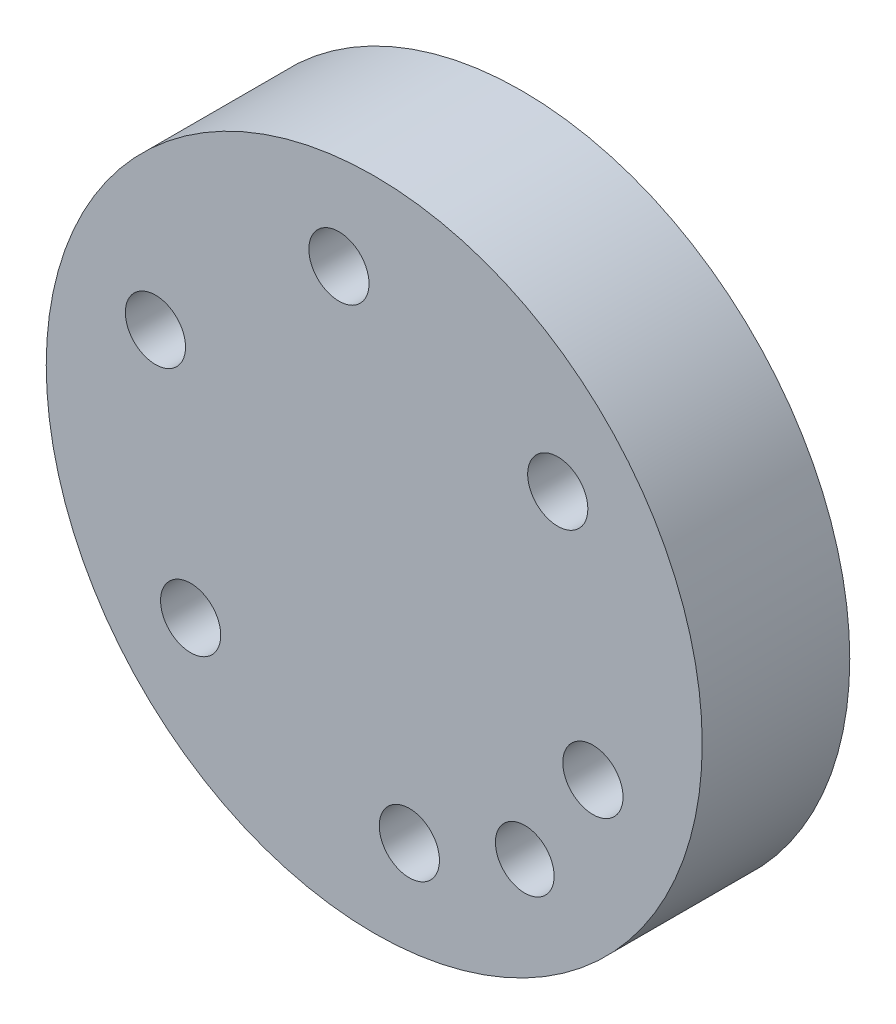
SolidWorks part; units mm, degrees
ref_plane "Front Plane" through (0, 0, 0) normal (0, 0, 1) x (1, 0, 0)
ref_plane "Top Plane" through (0, 0, 0) normal (0, 1, 0) x (1, 0, 0)
ref_plane "Right Plane" through (0, 0, 0) normal (1, 0, 0) x (0, 0, -1)
sketch "Sketch2" plane through (0, 0, 0) normal (0, 0, 1) x (1, 0, 0)
  circle A2 centre (22.3808, 278.1504) radius 88.7
  arc A4 (22.3808, 354.5504) -> (22.3808, 201.7504) centre (22.3808, 278.1504) ccw
  arc A5 (22.3808, 201.7504) -> (22.3808, 354.5504) centre (22.3808, 278.1504) ccw
  arc A6 (22.3808, 354.5504) -> (22.3808, 201.7504) centre (22.3808, 278.1504) ccw
  arc A7 (22.3808, 201.7504) -> (22.3808, 354.5504) centre (22.3808, 278.1504) ccw
  dimension "D2" = 177.4
  dimension "D1" = 0.2
extrude "Boss-Extrude1" add sketch "Sketch2" against normal blind 24.9
sketch "Sketch3" plane through (0, 0, 0) normal (0, 0, 1) x (1, 0, 0)
  line L0 (22.3808, 278.1504) -> (121.3474, 154.1978) construction
  circle A0 centre (63.0884, 227.1655) radius 7.9375
  circle A1 centre (22.3808, 278.1504) radius 88.7
  circle A2 centre (22.3808, 278.1504) radius 88.7
  circle A120 centre (12.8349, 340.868) radius 8.1375
  circle A121 centre (72.0102, 317.7343) radius 8.1375
  circle A122 centre (-36.7846, 301.2181) radius 8.1375
  circle A123 centre (-27.2648, 238.487) radius 8.1375
  circle A124 centre (31.8806, 215.335) radius 8.1375
  circle A125 centre (81.5193, 254.9712) radius 8.1375
  arc A126 (61.9965, 220.7534) -> (61.9965, 236.3127) centre (61.9965, 228.5331) ccw construction
  arc A127 (61.9965, 236.3127) -> (61.9965, 220.7534) centre (61.9965, 228.5331) ccw construction
  arc A128 (61.9965, 236.3127) -> (61.9965, 220.7534) centre (61.9965, 228.5331) ccw construction
  arc A129 (61.9965, 220.7534) -> (61.9965, 236.3127) centre (61.9965, 228.5331) ccw construction
  dimension "D2" = 16.275
  dimension "D3" = 15.875
  dimension "D4" = 1.75
  dimension "D1" = 0
extrude "Boss-Extrude2" add sketch "Sketch3" along normal blind 15
fillet "Fillet1" radius 2 1 edges at (71.0259, 227.1655, 0)
chamfer "Chamfer1" distance 4.5 distance2 8 1 edges at (98.7808, 278.1504, -24.9) first distance on face at (98.7808, 278.1504, -24.9)
fillet "Fillet2" radius 3 1 edges at (98.7808, 278.1504, -16.9)
fillet "Fillet3" radius 2 1 edges at (103.2808, 278.1504, -24.9)
sketch "Sketch4" plane through (0, 0, 0) normal (0, 0, -1) x (-1, 0, 0)
  circle A1 centre (27.2648, 238.487) radius 8.1375 construction
  circle A2 centre (-22.3808, 278.1504) radius 76.8
  circle A3 centre (-22.3808, 278.1504) radius 76.8
  circle A4 centre (-31.8806, 215.335) radius 8.1375 construction
  circle A5 centre (-63.0884, 227.1655) radius 7.9375 construction
  circle A6 centre (-81.5193, 254.9712) radius 8.1375 construction
  circle A7 centre (36.7846, 301.2181) radius 8.1375 construction
  circle A8 centre (-12.8349, 340.868) radius 8.1375 construction
  circle A9 centre (-72.0102, 317.7343) radius 8.1375 construction
  circle A10 centre (27.2648, 238.487) radius 8.1375
  circle A11 centre (-31.8806, 215.335) radius 8.1375
  circle A12 centre (-63.0884, 227.1655) radius 7.9375
  circle A13 centre (-81.5193, 254.9712) radius 8.1375
  circle A14 centre (36.7846, 301.2181) radius 8.1375
  circle A15 centre (-12.8349, 340.868) radius 8.1375
  circle A16 centre (-72.0102, 317.7343) radius 8.1375
  dimension "D1" = 0.4
extrude "Boss-Extrude3" add sketch "Sketch4" along normal offset from surface (16.3 mm away) 8.6 separate body up to face at (104.4505, 278.1504, -24.9)
